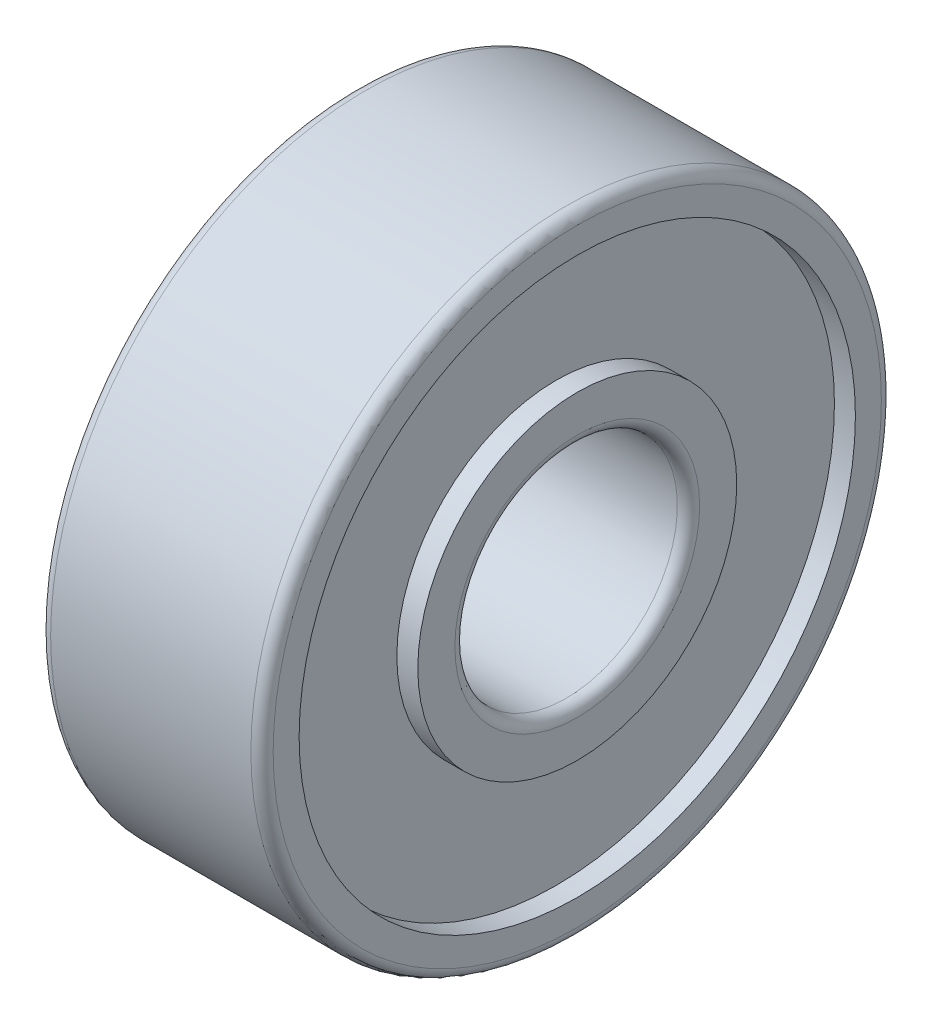
SolidWorks part; units mm, degrees
material "AISI 304"
ref_plane "前视基准面" through (0, 0, 0) normal (0, 0, 1) x (1, 0, 0)
ref_plane "上视基准面" through (0, 0, 0) normal (0, 1, 0) x (1, 0, 0)
ref_plane "右视基准面" through (0, 0, 0) normal (1, 0, 0) x (0, 0, -1)
sketch "草图1" plane through (0, 0, 0) normal (0, 0, 1) x (1, 0, 0)
  line L0 (0, 8.2) -> (0, 7.5)
  line L1 (0, 7.5) -> (0.565, 7.5)
  line L2 (0.565, 7.5) -> (0.565, 4.3)
  line L3 (0.565, 4.3) -> (0, 4.3)
  line L4 (0, 4.3) -> (0, 3.3)
  line L5 (0.3, 3) -> (5.7, 3)
  line L6 (6, 3.3) -> (6, 4.3)
  line L7 (6, 4.3) -> (5.435, 4.3)
  line L8 (5.435, 4.3) -> (5.435, 7.5)
  line L9 (5.435, 7.5) -> (6, 7.5)
  line L10 (6, 7.5) -> (6, 8.2)
  line L11 (5.7, 8.5) -> (0.3, 8.5)
  line L12 (5.7, 0) -> (0.3, 0) construction
  arc A0 (0, 3.3) -> (0.3, 3) centre (0.3, 3.3) ccw
  arc A1 (5.7, 3) -> (6, 3.3) centre (5.7, 3.3) ccw
  arc A2 (6, 8.2) -> (5.7, 8.5) centre (5.7, 8.2) ccw
  arc A3 (0.3, 8.5) -> (0, 8.2) centre (0.3, 8.2) ccw
revolve "旋转1" add sketch "草图1" angle 360 about L12 reverse direction yes
ref_plane "基准面1" through (3, 0, 0) normal (1, 0, 0) x (0, 0, -1)
ref_plane "to_housing XY" through (0, 0, 0) normal (1, 0, 0) x (0, 0, -1)
ref_plane "to_housing XZ" through (0, 0, 0) normal (0, -1, 0) x (-1, 0, 0)
ref_plane "to_housing YZ" through (0, 0, 0) normal (0, 0, -1) x (-1, 0, 0)
ref_axis "to_housing X" through (0, 0, 80.9) along (0, 0, -1)
ref_axis "to_housing Y" through (0, -50, 0) along (0, 1, 0)
ref_axis "to_housing Z" through (80.9, 0, 0) along (-1, 0, 0)
sketch3d "to_housing"
  point P0 (0, 0, 0)
ref_plane "to_housing_center XY" through (3, 0, 0) normal (1, 0, 0) x (0, 0, -1)
ref_plane "to_housing_center XZ" through (0, 0, 0) normal (0, -1, 0) x (-1, 0, 0)
ref_plane "to_housing_center YZ" through (0, 0, 0) normal (0, 0, -1) x (-1, 0, 0)
ref_axis "to_housing_center X" through (3, 0, 80.9) along (0, 0, -1)
ref_axis "to_housing_center Y" through (3, -50, 0) along (0, 1, 0)
ref_axis "to_housing_center Z" through (80.9, 0, 0) along (-1, 0, 0)
sketch3d "to_housing_center"
  point P0 (3, 0, 0)
